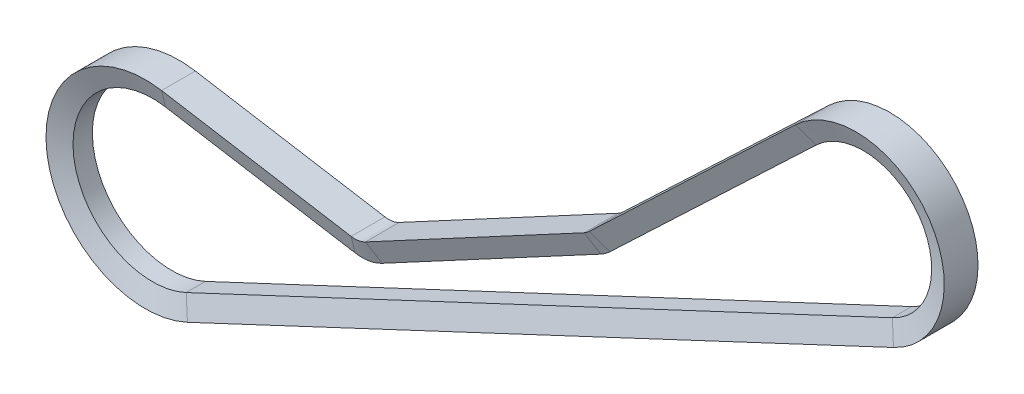
SolidWorks part; units mm, degrees
ref_plane "Front Plane" through (0, 0, 0) normal (0, 0, 1) x (1, 0, 0)
ref_plane "Top Plane" through (0, 0, 0) normal (0, 1, 0) x (1, 0, 0)
ref_plane "Right Plane" through (0, 0, 0) normal (1, 0, 0) x (0, 0, -1)
sketch "Sketch2" plane through (0, 0, 0) normal (0, 0, 1) x (1, 0, 0)
  line L0 (0, 0) -> (1, 0) construction
  line L1 (0, 0) -> (0, 1) construction
  line L12 (10.5645, -22.5202) -> (-188.5886, -115.9454)
  line L14 (-195.8872, -62.9753) -> (-142.4074, -71.8686)
  line L15 (-138.3646, -71.2006) -> (-76.6765, -38.1161)
  line L16 (-75.3086, -37.128) -> (-17.1156, 18.0506)
  arc A4 (-188.5886, -115.9454) -> (-195.8872, -62.9753) centre (-200.4803, -90.596) cw
  arc A7 (-17.1156, 18.0506) -> (10.5645, -22.5202) centre (0, 0) cw
  arc A8 (-142.4074, -71.8686) -> (-138.3646, -71.2006) centre (-141.3658, -65.6046) ccw
  arc A9 (-76.6765, -38.1161) -> (-75.3086, -37.128) centre (-79.6778, -32.5201) ccw
ref_plane "Plane4" through (-17.1156, 18.0506, 0) normal (0.7257, 0.6881, 0) x (0.6881, -0.7257, 0)
sketch "Sketch3" plane through (-17.1156, 18.0506, 0) normal (0.7257, 0.6881, 0) x (0.6881, -0.7257, 0)
  line L0 (0, -4.7625) -> (0, 4.7625)
  line L1 (0, -4.7625) -> (5.588, -2.7286)
  line L2 (5.588, -2.7286) -> (5.588, 2.7286)
  line L3 (5.588, 2.7286) -> (0, 4.7625)
  line L4 (0, 0) -> (5.588, 0) construction
  dimension "D1" = 9.525
  dimension "D2" = 5.588
  dimension "D3" = 40
sweep "Sweep1" add profiles "Sketch3" path "Sketch2"
